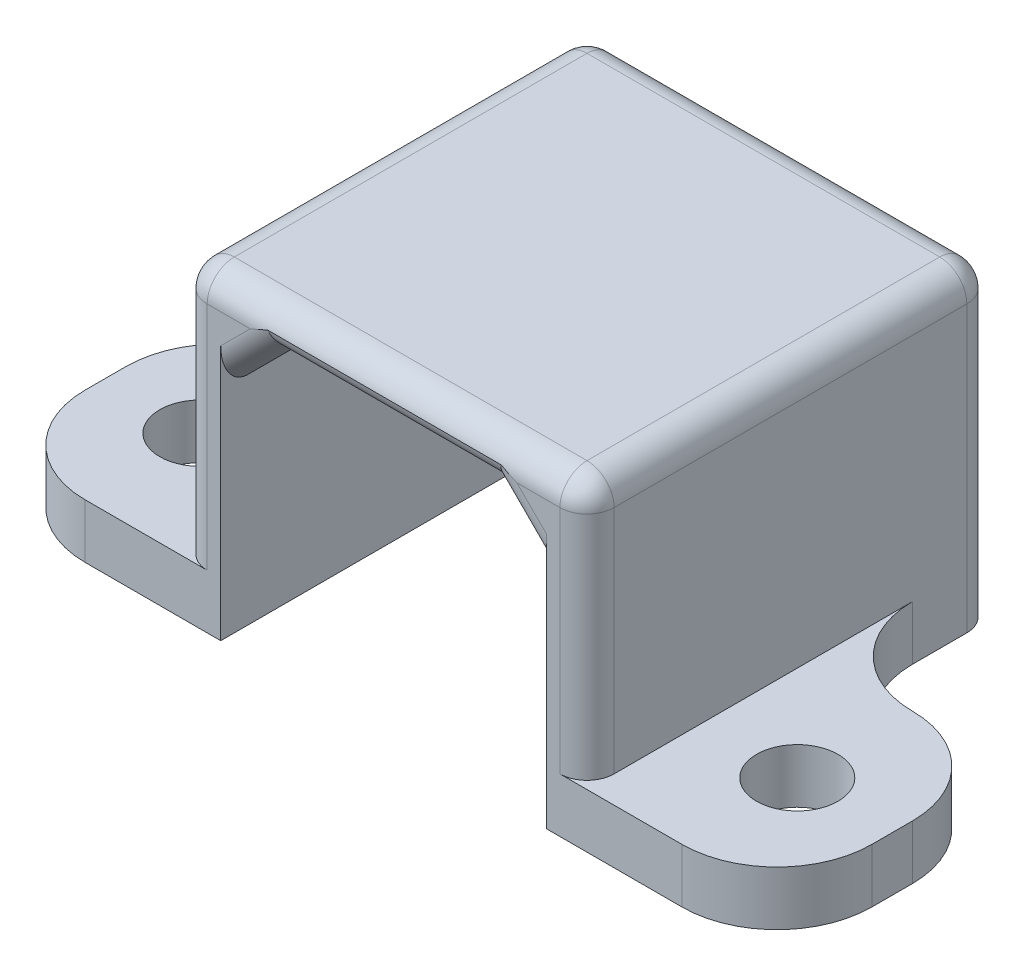
SolidWorks part; units mm, degrees
ref_plane "Front Plane" through (0, 0, 0) normal (0, 0, 1) x (1, 0, 0)
ref_plane "Top Plane" through (0, 0, 0) normal (0, 1, 0) x (1, 0, 0)
ref_plane "Right Plane" through (0, 0, 0) normal (1, 0, 0) x (0, 0, -1)
sketch "Sketch2" plane through (0, 0, 0) normal (0, 0, 1) x (1, 0, 0)
  line L1 (-7.5, -5.75) -> (7.5, -5.75)
  line L2 (-7.5, -5.75) -> (-7.5, 5.75)
  line L3 (-7.5, 5.75) -> (7.5, 5.75)
  line L4 (7.5, -5.75) -> (7.5, 5.75)
  line L5 (-7.5, -5.75) -> (7.5, 5.75) construction
  line L6 (-7.5, 5.75) -> (7.5, -5.75) construction
  point P0 (0, 0)
  dimension "D1" = 11.5
  dimension "D2" = 15
extrude "Boss-Extrude1" add sketch "Sketch2" along normal blind 15
sketch "Sketch3" plane through (0, 0, 15) normal (0, 0, 1) x (1, 0, 0)
  line L0 (6, -5.75) -> (6, 4.25)
  line L5 (6, 4.25) -> (-6, 4.25)
  line L6 (-6, 4.25) -> (-6, -5.75)
  line L7 (7.5, -5.75) -> (7.5, 5.75) construction
  line L8 (7.5, 5.75) -> (-7.5, 5.75) construction
  line L9 (-7.5, 5.75) -> (-7.5, -5.75) construction
  line L10 (7.5, -5.75) -> (7.5, 5.75) construction
  line L11 (7.5, 5.75) -> (-7.5, 5.75) construction
  line L12 (-7.5, 5.75) -> (-7.5, -5.75) construction
  line L13 (-6, -5.75) -> (6, -5.75)
  dimension "D1" = 1.5
extrude "Cut-Extrude1" cut sketch "Sketch3" against normal blind 15
sketch "Sketch4" plane through (-7.5, 0, 0) normal (-1, 0, 0) x (0, 0, 1)
  line L1 (15, -5.75) -> (6.5, -5.75)
  line L2 (15, -5.75) -> (15, -3.75)
  line L3 (15, -3.75) -> (6.5, -3.75)
  line L4 (6.5, -5.75) -> (6.5, -3.75)
  dimension "D1" = 2
  dimension "D2" = 8.5
extrude "Boss-Extrude2" add sketch "Sketch4" along normal blind 7
sketch "Sketch5" plane through (0, -3.75, 0) normal (0, 1, 0) x (1, 0, 0)
  circle A0 centre (-11, -10.75) radius 1.5
  dimension "D1" = 3
extrude "Cut-Extrude2" cut sketch "Sketch5" against normal blind 7
mirror "Mirror3" about plane through (0, 0, 0) normal (1, 0, 0) of "Boss-Extrude2", "Cut-Extrude2"
sketch "Sketch6" plane through (0, 0, 15) normal (0, 0, 1) x (1, 0, 0)
  line L0 (-6, 2.25) -> (-4, 4.25)
  line L1 (-6, 4.25) -> (-6, -5.75) construction
  line L2 (6, 4.25) -> (-6, 4.25) construction
  line L3 (-4, 4.25) -> (-6, 4.25)
  line L4 (-6, 4.25) -> (-6, 2.25)
  line L5 (0, -6.325) -> (0, 6.325) construction
  line L6 (4, 4.25) -> (6, 4.25)
  line L7 (6, 2.25) -> (4, 4.25)
  line L8 (6, 4.25) -> (6, 2.25)
  dimension "D1" = 2
  dimension "D2" = 2
extrude "Boss-Extrude3" add sketch "Sketch6" against normal up to surface (15 mm away) up to face at (0, -0.375, 0)
sketch "Sketch7" plane through (0, 4.25, 0) normal (0, -1, 0) x (1, 0, 0)
  line L0 (6, 0) -> (6, 15) construction
  line L1 (-6, 4.3) -> (6, 4.3)
  line L2 (-6, 4.3) -> (-6, 5)
  line L3 (-6, 5) -> (6, 5)
  line L4 (6, 4.3) -> (6, 5)
  line L5 (-6, 4.3) -> (6, 5) construction
  line L6 (-6, 5) -> (6, 4.3) construction
  line L7 (4, 15) -> (-4, 15) construction
  line L8 (6, 0) -> (6, 15) construction
  line L9 (-6, 7) -> (6, 7)
  line L10 (-6, 7) -> (-6, 7.7)
  line L11 (-6, 7.7) -> (6, 7.7)
  line L12 (6, 7) -> (6, 7.7)
  line L13 (-6, 7) -> (6, 7.7) construction
  line L14 (-6, 7.7) -> (6, 7) construction
  point P0 (0, 4.65)
  point P9 (0, 7.35)
  dimension "D1" = 0.7
  dimension "D2" = 10
  dimension "D3" = 12
  dimension "D4" = 0.7
  dimension "D5" = 12
  dimension "D6" = 2
extrude "Cut-Extrude3" cut sketch "Sketch7" along normal blind 3
fillet "Fillet2" radius 3.5 6 edges at (-7.5, -4.75, 6.5) (7.5, -4.75, 6.5) (14.5, -4.75, 15) (14.5, -4.75, 6.5) (-14.5, -4.75, 15) (-14.5, -4.75, 6.5)
fillet "Fillet3" radius 1 14 edges at (0, 4.25, 0) (0, 4.25, 15) (-5, 3.25, 15) (5, 3.25, 15) (5, 3.25, 0) (-5, 3.25, 0) (7.5, 0, 0) (0, 5.75, 0) (7.5, 5.75, 7.5) (7.5, 1, 15) (-7.5, 0, 0) (-7.5, 5.75, 7.5) (0, 5.75, 15) (-7.5, 1, 15)
